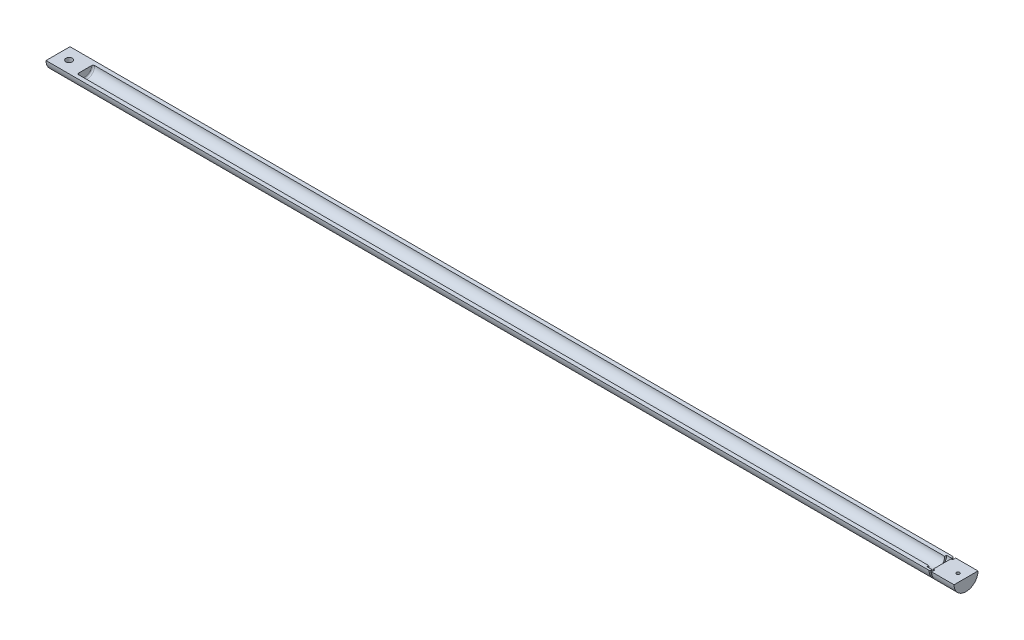
SolidWorks part; units mm, degrees
ref_plane "Front Plane" through (0, 0, 0) normal (0, 0, 1) x (1, 0, 0)
ref_plane "Top Plane" through (0, 0, 0) normal (0, 1, 0) x (1, 0, 0)
ref_plane "Right Plane" through (0, 0, 0) normal (1, 0, 0) x (0, 0, -1)
sketch "Sketch1" plane through (0, 0, 0) normal (0, 1, 0) x (1, 0, 0)
  line L1 (0, 0) -> (1803.4, 0)
  line L2 (0, 0) -> (0, 57.15)
  line L3 (0, 57.15) -> (1803.4, 57.15)
  line L4 (1803.4, 0) -> (1803.4, 57.15)
  dimension "blank_length" = 1803.4
  dimension "blank_width" = 57.15
extrude "wood block" add sketch "Sketch1" along normal blind 28.575
ref_plane "Plane1" through (0, 0, -28.575) normal (0, 0, 1) x (1, 0, 0)
sketch "Sketch2" plane through (0, 0, -28.575) normal (0, 0, 1) x (1, 0, 0)
  line L0 (1755.775, 28.575) -> (0, 28.575)
  line L2 (0, 12.7) -> (1755.775, 12.7)
  line L5 (0, 28.575) -> (0, 0) construction
  line L6 (0, 12.7) -> (0, 28.575)
  line L7 (1755.775, 12.7) -> (1755.775, 28.575)
  dimension "inner_bore_radius" = 15.875
  dimension "finished_length" = 1755.775
revolve "inner bore" cut sketch "Sketch2" angle 360 about L0
sketch "Sketch9" plane through (0, 0, -28.575) normal (0, 0, 1) x (1, 0, 0)
  line L0 (0, 28.575) -> (0, 0) construction
  line L1 (1755.775, 28.575) -> (1745.234, 28.575)
  line L2 (1755.775, 28.575) -> (1755.775, 9.017)
  line L3 (1755.775, 9.017) -> (1745.234, 9.017)
  line L4 (1745.234, 28.575) -> (1745.234, 9.017)
  line L5 (0, 28.575) -> (1803.4, 28.575) construction
  dimension "flange_foot_recess" = 10.541
  dimension "finished_length" = 1755.775
  dimension "flange_counterbore_radius" = 19.558
revolve "flanged foot relief" cut sketch "Sketch9" angle 360 about L1
ref_axis "Axis1" through (-15.875, 28.575, -28.575) along (1, 0, 0)
sketch "Sketch10" plane through (0, 0, 0) normal (-1, 0, 0) x (0, 0, 1)
  line L1 (-57.15, 0) -> (0, 0)
  line L2 (-57.15, 0) -> (-57.15, 28.575)
  line L3 (-57.15, 28.575) -> (0, 28.575)
  line L4 (0, 0) -> (0, 28.575)
  line L5 (-57.15, 0) -> (0, 28.575) construction
  line L6 (-57.15, 28.575) -> (0, 0) construction
  point P4 (-28.575, 14.2875)
extrude "Boss-Extrude1" add sketch "Sketch10" against normal blind 53.975
fillet "Fillet1" radius 3.175 1 edges at (53.975, 12.7, -28.575)
sketch "Sketch5" plane through (0, 28.575, 0) normal (0, 1, 0) x (1, 0, 0)
  line L0 (-15.7163, 28.575) -> (15.7163, 28.575) construction
  line L1 (0, 44.45) -> (0, 12.7) construction
  line L2 (15.8369, 28.575) -> (0, 28.575) construction
  line L3 (0, 44.45) -> (0, 12.7) construction
  circle A0 centre (22.225, 28.575) radius 6.3881
  dimension "mouthpiece_hole" = 12.7762
  dimension "mouthpiece_location" = 22.225
extrude "mouthpiece hole" cut sketch "Sketch5" against normal blind 21.59
sketch "Sketch6" plane through (0, 28.575, 0) normal (0, 1, 0) x (1, 0, 0)
  line L0 (1803.4, 28.575) -> (1787.525, 28.575) construction
  line L1 (1803.4, 0) -> (1803.4, 57.15) construction
  circle A1 centre (1787.525, 28.575) radius 3.175
  dimension "dowel_pin_diameter" = 6.35
  dimension "dowel_pin_location" = 15.875
extrude "dowel pin hole" cut sketch "Sketch6" against normal blind 15.24
sketch "Sketch8" plane through (0, 0, 0) normal (0, -1, 0) x (1, 0, 0)
  line L0 (22.225, -28.575) -> (713.359, -28.575) construction
  circle A0 centre (22.225, -28.575) radius 8.128
  circle A1 centre (713.359, -28.575) radius 8.128
  dimension "tube_diameter" = 16.256
  dimension "bracket_length" = 691.134
extrude "mounting holes" cut sketch "Sketch8" against normal blind 10.3124
chamfer "Chamfer1" distance 16.7386 angle 45 2 edges at (901.7, 0, -57.15) (901.7, 0, 0)
sketch "Sketch3" plane through (1803.4, 0, 0) normal (1, 0, 0) x (0, 0, -1)
  line L0 (28.575, 15.7163) -> (28.575, -15.7163) construction
  line L1 (0, 28.575) -> (57.15, 28.575) construction
  circle A0 centre (28.575, 28.575) radius 23.8125
  dimension "outer_diameter" = 47.625
extrude "outer diameter" cut sketch "Sketch3" against normal through all flip side to cut
sketch "Sketch7" plane through (0, 28.575, 0) normal (0, 1, 0) x (1, 0, 0)
  line L0 (1803.4, 4.7625) -> (0, 4.7625) construction
  line L1 (1755.775, 4.7625) -> (1758.95, 4.7625)
  line L2 (1755.775, 4.7625) -> (1755.775, 11.1125)
  line L3 (1755.775, 11.1125) -> (1758.95, 11.1125)
  line L4 (1758.95, 4.7625) -> (1758.95, 11.1125)
  line L5 (1755.775, 12.7) -> (1755.775, 4.7625) construction
  line L6 (1803.4, 4.7625) -> (1803.4, 52.3875) construction
  line L7 (0, 44.45) -> (0, 12.7) construction
  dimension "finished_length" = 1755.775
  dimension "groove_width" = 3.175
  dimension "groove_depth" = 6.35
  dimension "groove_location" = 47.625
revolve "end length locator" cut sketch "Sketch7" angle 360 about axis through (-15.875, 28.575, -28.575) along (1, 0, 0)
chamfer "Chamfer at foot" distance 1.905 angle 45 1 edges at (1755.775, 4.7625, -28.575)
equation "\"g_body_OD\"= 47.625mm"
equation "\"g_body_ID\"= 31.75mm"
equation "\"g_body_L_finished\"= 1755.775mm"
equation "\"g_body_L_blank\"= 1803.4mm"
equation "\"g_body_blank_W\"= 57.15mm"
equation "\"g_dowel_OD\"= 6.35mm"
equation "\"g_thru_passage_OD\"= 12.7mm"
equation "\"g_mp_tube_OD\"= 15.875mm"
equation "\"c_glue_gap\"= 0.0762mm"
equation "\"c_slip_fit\"= 0.381mm"
equation "\"c_dowel_clearance\"= 0mm"
equation "\"thickness@wood block\"= \"g_body_blank_W\" / 2"
equation "\"blank_length@Sketch1\"= \"g_body_L_blank\""
equation "\"blank_width@Sketch1\"= \"g_body_blank_W\""
equation "\"inner_bore_radius@Sketch2\"= \"g_body_ID\" / 2"
equation "\"outer_diameter@Sketch3\"= \"g_body_OD\""
equation "\"finished_length@Sketch7\"= \"g_body_L_finished\""
equation "\"dowel_pin_diameter@Sketch6\"= \"g_dowel_OD\" + \"c_dowel_clearance\""
equation "\"tube_diameter@Sketch8\"= \"g_mp_tube_OD\" + \"c_slip_fit\""
equation "\"mouthpiece_hole@Sketch5\"= \"g_thru_passage_OD\" + \"c_glue_gap\""
